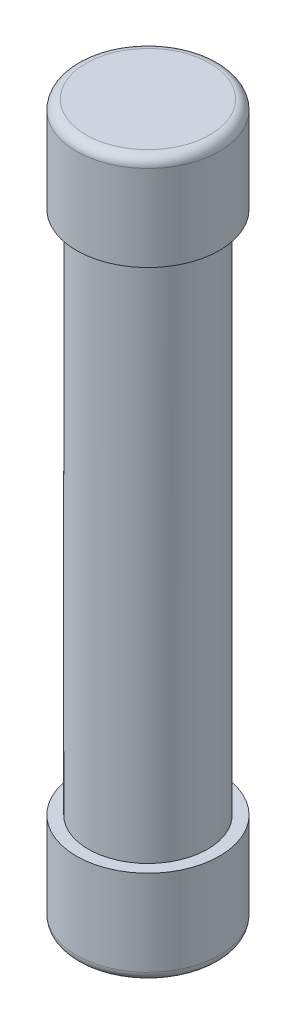
SolidWorks part; units mm, degrees
ref_plane "Front Plane" through (0, 0, 0) normal (0, 0, 1) x (1, 0, 0)
ref_plane "Top Plane" through (0, 0, 0) normal (0, 1, 0) x (1, 0, 0)
ref_plane "Right Plane" through (0, 0, 0) normal (1, 0, 0) x (0, 0, -1)
sketch "Sketch1" plane through (0, 0, 0) normal (0, 1, 0) x (1, 0, 0)
  circle A0 centre (0, 0) radius 12.5
  dimension "D1" = 25
extrude "Boss-Extrude1" add sketch "Sketch1" along normal mid plane 150
sketch "Sketch2" plane through (0, 75, 0) normal (0, 1, 0) x (1, 0, 0)
  circle A0 centre (0, 0) radius 15
  dimension "D1" = 30
extrude "Boss-Extrude2" add sketch "Sketch2" against normal blind 20
mirror "Mirror1" about plane through (0, 0, 0) normal (0, 1, 0) of "Boss-Extrude2"
fillet "Fillet1" radius 2 2 edges at (0, 75, 15) (0, -75, 15)
shell "Shell2" thickness 1
